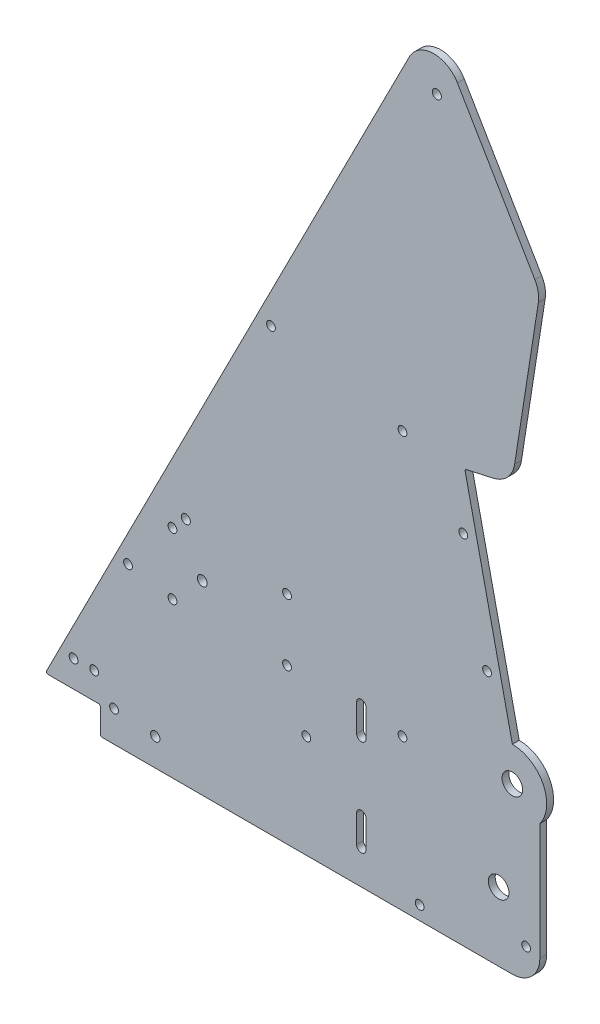
SolidWorks part; units mm, degrees
other "Markup1"
sketch "Sketch5"
ref_plane "Front Plane" through (0, 0, 0) normal (0, 0, 1) x (1, 0, 0)
ref_plane "Top Plane" through (0, 0, 0) normal (0, 1, 0) x (1, 0, 0)
ref_plane "Right Plane" through (0, 0, 0) normal (1, 0, 0) x (0, 0, -1)
sketch "Sketch1" plane through (0, 0, 0) normal (0, 0, 1) x (1, 0, 0)
  line L1 (228.6, -12.7) -> (228.6, 53.975)
  line L2 (178.7547, 351.4131) -> (0, 0)
  line L3 (228.6, 266.7) -> (178.7547, 351.4131)
  line L5 (0, 0) -> (25.4, 0)
  line L6 (25.4, 0) -> (25.4, -12.7)
  line L7 (25.4, -12.7) -> (228.6, -12.7)
  line L9 (215.9, 79.375) -> (193.9097, 178.5667)
  line L10 (193.9097, 178.5667) -> (215.6079, 183.377)
  line L11 (215.6079, 183.377) -> (228.6, 266.7)
  arc A0 (228.6, 53.975) -> (215.9, 79.375) centre (215.9, 63.5) ccw
  dimension "D7" = 12.7
  dimension "D8" = 76.2
  dimension "D10" = 31.75
  dimension "D2" = 279.4
  dimension "D3" = 25.4
  dimension "D4" = 215.9
  dimension "D5" = 394.2644
  dimension "D6" = 203.2
  dimension "D9" = 63.039
  dimension "D11" = 101.6
  dimension "D12" = 12.5
  dimension "D13" = 22.225
extrude "Boss-Extrude1" add sketch "Sketch1" along normal blind 3.175
sketch "Sketch2" plane through (0, 0, 3.175) normal (0, 0, 1) x (1, 0, 0)
  line L0 (178.7547, 351.4131) -> (0, 0) construction
  line L1 (25.4, -12.7) -> (228.6, -12.7) construction
  line L2 (215.9, 79.375) -> (193.9097, 178.5667) construction
  line L3 (193.9097, 178.5667) -> (215.6079, 183.377) construction
  line L4 (215.9, 79.375) -> (193.9097, 178.5667) construction
  line L5 (64.9432, 94.0578) -> (72.5445, 73.1732) construction
  line L6 (64.9432, 94.0578) -> (103.3734, 94.0578) construction
  line L10 (228.6, -12.7) -> (228.6, 53.975) construction
  circle A0 centre (64.9432, 94.0578) radius 2.0955
  circle A1 centre (180.975, 322.1643) radius 2.0955
  circle A2 centre (72.5445, 73.1732) radius 2.286
  circle A3 centre (193.2078, 152.3944) radius 2.032
  circle A4 centre (215.9, 63.5) radius 4.7625
  circle A7 centre (173.0375, -6.35) radius 2.032
  circle A8 centre (204.203, 102.7985) radius 2.032
  circle A26 centre (209.55, 19.05) radius 4.7625
  arc A30 (228.6, 53.975) -> (215.9, 79.375) centre (215.9, 63.5) ccw construction
  circle A31 centre (165.1, 179.3875) radius 2.032
  circle A35 centre (111.724, 87.4607) radius 2.032
  circle A36 centre (111.724, 58.8857) radius 2.032
  circle A37 centre (58.765, 58.8857) radius 2.032
  circle A38 centre (58.765, 87.4607) radius 2.032
  circle A39 centre (111.724, 58.8857) radius 1.905 construction
  circle A42 centre (111.724, 87.4607) radius 1.905 construction
  circle A43 centre (58.765, 58.8857) radius 1.905 construction
  circle A44 centre (58.765, 87.4607) radius 1.905 construction
  dimension "D3" = 4.191
  dimension "D5" = 4.191
  dimension "D9" = 4.572
  dimension "D20" = 9.525
  dimension "D23" = 9.525
  dimension "D18" = 4.064
  dimension "D26" = 4.064
  dimension "D14" = 4.064
  dimension "D10" = 4.064
  dimension "D2" = 15.24
  dimension "D6" = 15.24
  dimension "D7" = 22.225
  dimension "D21" = 44.45
  dimension "D22" = 6.35
  dimension "D19" = 160.3375
  dimension "D24" = 44.45
  dimension "D25" = 6.35
  dimension "D27" = 25.4
  dimension "D28" = 50.8
  dimension "D29" = 6.35
  dimension "D17" = 6.35
  dimension "D33" = 55.5625
  dimension "D15" = 114.3
  dimension "D4" = 180.975
  dimension "D8" = 70
extrude "Cut-Extrude1" cut sketch "Sketch2" against normal through all
sketch "Sketch7" plane through (0, 0, 3.175) normal (0, 0, 1) x (1, 0, 0)
  line L0 (146.05, 3.175) -> (146.05, 15.875) construction
  line L1 (143.891, 3.175) -> (143.891, 15.875)
  line L2 (148.209, 3.175) -> (148.209, 15.875)
  line L3 (146.05, 47.625) -> (146.05, 60.325) construction
  line L4 (143.891, 47.625) -> (143.891, 60.325)
  line L5 (148.209, 47.625) -> (148.209, 60.325)
  line L6 (25.4, -12.7) -> (228.6, -12.7) construction
  line L12 (228.6, -12.7) -> (228.6, 53.975) construction
  line L13 (25.4, -12.7) -> (228.6, -12.7) construction
  arc A0 (143.891, 3.175) -> (148.209, 3.175) centre (146.05, 3.175) ccw
  arc A1 (148.209, 15.875) -> (143.891, 15.875) centre (146.05, 15.875) ccw
  arc A2 (143.891, 47.625) -> (148.209, 47.625) centre (146.05, 47.625) ccw
  arc A3 (148.209, 60.325) -> (143.891, 60.325) centre (146.05, 60.325) ccw
  circle A8 centre (50.8, 0) radius 2.159
  point P2 (146.05, 9.525)
  point P9 (146.05, 53.975)
  dimension "D1" = 4.318
  dimension "D5" = 4.318
  dimension "D2" = 12.7
  dimension "D3" = 12.7
  dimension "D4" = 44.45
  dimension "D6" = 95.25
  dimension "D7" = 82.55
  dimension "D8" = 15.875
  dimension "D9" = 12.7
extrude "Cut-Extrude2" cut sketch "Sketch7" against normal through all
sketch "Sketch10" plane through (0, 0, 3.175) normal (0, 0, 1) x (1, 0, 0)
  circle A0 centre (120.65, 34.925) radius 2.032
  circle A1 centre (165.1, 57.15) radius 2.032
  circle A2 centre (13.0465, 12.3347) radius 2.032
  circle A3 centre (22.5715, 12.3347) radius 2.032
  circle A4 centre (38.2114, 62.6398) radius 2.032
  dimension "D1" = 4.064
  dimension "D3" = 34.925
  dimension "D2" = 120.65
  dimension "D4" = 63.5
  dimension "D5" = 69.85
extrude "Cut-Extrude3" cut sketch "Sketch10" against normal up to next
fillet "Fillet1" radius 12.7 4 edges at (228.6, -12.7, 1.5875) (178.7547, 351.4131, 1.5875) (215.6079, 183.377, 1.5875) (228.6, 266.7, 1.5875)
fillet "Fillet2" radius 0.7937 4 edges at (25.4, -12.7, 1.5875) (25.4, 0, 1.5875) (193.9097, 178.5667, 1.5875) (0, 0, 1.5875)
sketch "Sketch12" plane through (0, 0, 3.175) normal (0, 0, 1) x (1, 0, 0)
  circle A0 centre (31.75, 1.5875) radius 2.032
  circle A1 centre (173.0375, -6.35) radius 2.032
  circle A2 centre (222.25, 1.5875) radius 2.032
  dimension "D1" = 4.064
extrude "Cut-Extrude5" cut sketch "Sketch12" against normal through all
sketch "Sketch13" plane through (0, 0, 3.175) normal (0, 0, 1) x (1, 0, 0)
  line L0 (168.2448, 330.7518) -> (0.5868, 1.1536) construction
  circle A0 centre (104.3218, 191.08) radius 2.032
  dimension "D2" = 4.064
  dimension "D1" = 6.35
extrude "Cut-Extrude6" cut sketch "Sketch13" against normal through all
equation "\"D6@Sketch2\"=\"D2@Sketch2\""
